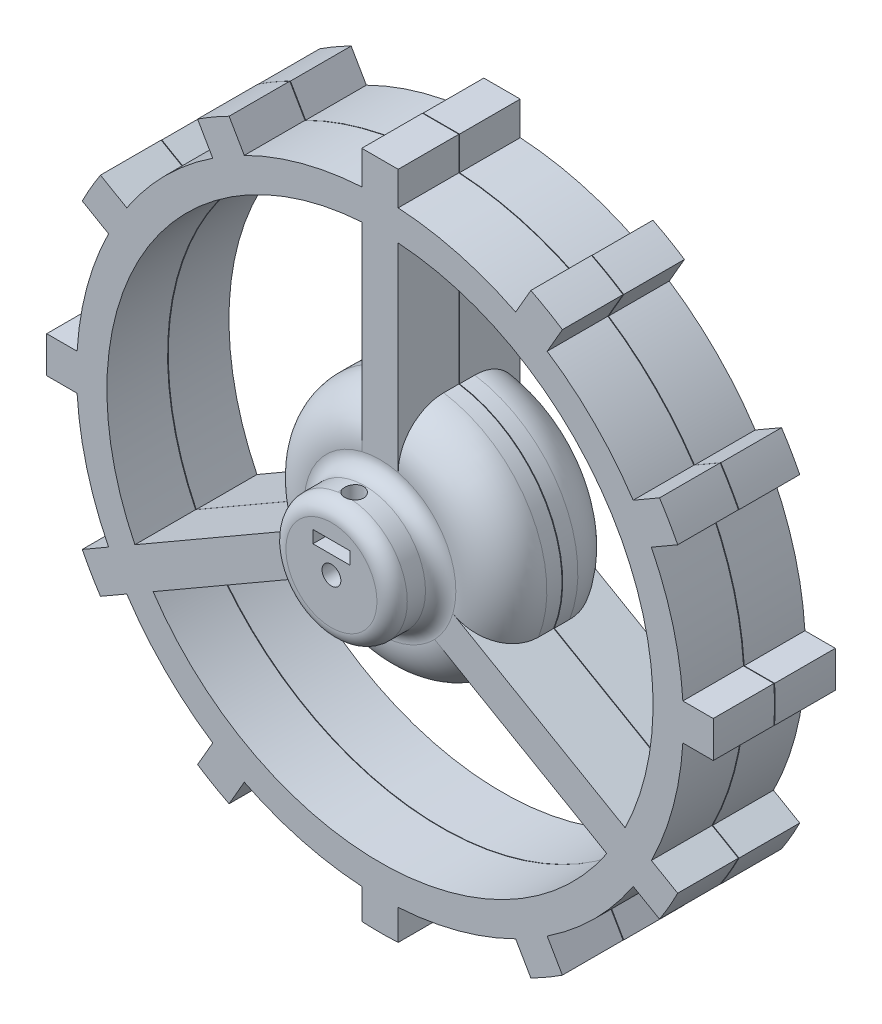
SolidWorks part; units mm, degrees
ref_plane "Front Plane" through (0, 0, 0) normal (0, 0, 1) x (1, 0, 0)
ref_plane "Top Plane" through (0, 0, 0) normal (0, 1, 0) x (1, 0, 0)
ref_plane "Right Plane" through (0, 0, 0) normal (1, 0, 0) x (0, 0, -1)
sketch "Sketch1" plane through (0, 0, 0) normal (0, 0, 1) x (1, 0, 0)
  line L0 (0, 50) -> (0, 55)
  line L1 (3, 49.9099) -> (3, 54.9181)
  line L2 (-3, 49.9099) -> (-3, 54.9181)
  line L3 (-3, 50) -> (-3, 55) construction
  line L4 (3, 50) -> (3, 55) construction
  line L5 (-3, 54.9181) -> (-3, 55.4203)
  line L6 (-3, 55.4203) -> (3, 55.4181)
  line L7 (3, 55.4181) -> (3, 54.9181)
  line L8 (0, 50) -> (0, 55) construction
  line L9 (0, 50) -> (0, 20)
  line L10 (22.3569, 44.7233) -> (24.861, 49.0605)
  line L11 (27.553, 41.7233) -> (30.0571, 46.0605)
  line L12 (25.1121, 49.4954) -> (30.3071, 46.4935)
  line L13 (30.3071, 46.4935) -> (30.0571, 46.0605)
  line L14 (24.861, 49.0605) -> (25.1121, 49.4954)
  line L15 (-3, 50) -> (-3, 20) construction
  line L17 (41.7233, 27.553) -> (46.0605, 30.0571)
  line L18 (44.7233, 22.3569) -> (49.0605, 24.861)
  line L19 (46.4954, 30.3082) -> (49.4935, 25.111)
  line L20 (49.4935, 25.111) -> (49.0605, 24.861)
  line L21 (46.0605, 30.0571) -> (46.4954, 30.3082)
  line L22 (3, 50) -> (3, 20) construction
  line L23 (-3, 50) -> (-3, 55)
  line L24 (49.9099, 3) -> (54.9181, 3)
  line L25 (49.9099, -3) -> (54.9181, -3)
  line L26 (55.4203, 3) -> (55.4181, -3)
  line L27 (55.4181, -3) -> (54.9181, -3)
  line L28 (54.9181, 3) -> (55.4203, 3)
  line L31 (44.7233, -22.3569) -> (49.0605, -24.861)
  line L32 (41.7233, -27.553) -> (46.0605, -30.0571)
  line L33 (49.4954, -25.1121) -> (46.4935, -30.3071)
  line L34 (46.4935, -30.3071) -> (46.0605, -30.0571)
  line L35 (49.0605, -24.861) -> (49.4954, -25.1121)
  line L37 (43.3013, -25) -> (17.3205, -10)
  line L38 (27.553, -41.7233) -> (30.0571, -46.0605)
  line L39 (22.3569, -44.7233) -> (24.861, -49.0605)
  line L40 (30.3082, -46.4954) -> (25.111, -49.4935)
  line L41 (25.111, -49.4935) -> (24.861, -49.0605)
  line L42 (30.0571, -46.0605) -> (30.3082, -46.4954)
  line L44 (-3, 50) -> (-3, 19.7737)
  line L45 (3, -49.9099) -> (3, -54.9181)
  line L46 (-3, -49.9099) -> (-3, -54.9181)
  line L47 (3, -55.4203) -> (-3, -55.4181)
  line L48 (-3, -55.4181) -> (-3, -54.9181)
  line L49 (3, -54.9181) -> (3, -55.4203)
  line L51 (3, 50) -> (3, 55)
  line L52 (-22.3569, -44.7233) -> (-24.861, -49.0605)
  line L53 (-27.553, -41.7233) -> (-30.0571, -46.0605)
  line L54 (-25.1121, -49.4954) -> (-30.3071, -46.4935)
  line L55 (-30.3071, -46.4935) -> (-30.0571, -46.0605)
  line L56 (-24.861, -49.0605) -> (-25.1121, -49.4954)
  line L58 (3, 50) -> (3, 19.7737)
  line L59 (-41.7233, -27.553) -> (-46.0605, -30.0571)
  line L60 (-44.7233, -22.3569) -> (-49.0605, -24.861)
  line L61 (-46.4954, -30.3082) -> (-49.4935, -25.111)
  line L62 (-49.4935, -25.111) -> (-49.0605, -24.861)
  line L63 (-46.0605, -30.0571) -> (-46.4954, -30.3082)
  line L65 (-43.3013, -25) -> (-17.3205, -10)
  line L66 (-49.9099, -3) -> (-54.9181, -3)
  line L67 (-49.9099, 3) -> (-54.9181, 3)
  line L68 (-55.4203, -3) -> (-55.4181, 3)
  line L69 (-55.4181, 3) -> (-54.9181, 3)
  line L70 (-54.9181, -3) -> (-55.4203, -3)
  line L73 (-44.7233, 22.3569) -> (-49.0605, 24.861)
  line L74 (-41.7233, 27.553) -> (-46.0605, 30.0571)
  line L75 (-49.4954, 25.1121) -> (-46.4935, 30.3071)
  line L76 (-46.4935, 30.3071) -> (-46.0605, 30.0571)
  line L77 (-49.0605, 24.861) -> (-49.4954, 25.1121)
  line L80 (-27.553, 41.7233) -> (-30.0571, 46.0605)
  line L81 (-22.3569, 44.7233) -> (-24.861, 49.0605)
  line L82 (-30.3082, 46.4954) -> (-25.111, 49.4935)
  line L83 (-25.111, 49.4935) -> (-24.861, 49.0605)
  line L84 (-30.0571, 46.0605) -> (-30.3082, 46.4954)
  line L87 (-41.8013, -27.5981) -> (-46.1314, -30.0981)
  line L88 (-41.8013, -27.5981) -> (-15.6245, -12.4849)
  line L89 (-44.8013, -22.4019) -> (-49.1314, -24.9019)
  line L90 (-44.8013, -22.4019) -> (-18.6245, -7.2888)
  line L91 (44.8013, -22.4019) -> (49.1314, -24.9019)
  line L92 (44.8013, -22.4019) -> (18.6245, -7.2888)
  line L93 (41.8013, -27.5981) -> (46.1314, -30.0981)
  line L94 (41.8013, -27.5981) -> (15.6245, -12.4849)
  line L96 (41.8013, -27.5981) -> (-1.5, -2.5981) construction
  line L98 (43.3013, -25) -> (0, 0) construction
  line L100 (44.8013, -22.4019) -> (1.5, 2.5981) construction
  line L103 (-44.8013, -22.4019) -> (-1.5, 2.5981) construction
  line L105 (-43.3013, -25) -> (0, 0) construction
  line L107 (-41.8013, -27.5981) -> (1.5, -2.5981) construction
  line L109 (3, -5.1962) -> (1.5, -2.5981) [skipped]
  line L110 (1.55, 0) -> (0, 0) [skipped]
  line L111 (1.3423, 0.775) -> (0, 0) [skipped]
  line L112 (0.775, 1.3423) -> (0, 0) [skipped]
  line L113 (-0.775, 1.3423) -> (0, 0) [skipped]
  line L114 (-1.3423, 0.775) -> (0, 0) [skipped]
  line L115 (-1.55, 0) -> (0, 0) [skipped]
  line L116 (-0.775, -1.3423) -> (0, 0) [skipped]
  line L117 (0, -1.55) -> (0, 0) [skipped]
  line L118 (-25, 43.3013) -> (-27.5, 47.6314) [skipped]
  line L119 (25, 43.3013) -> (27.5, 47.6314) [skipped]
  line L120 (43.3013, 25) -> (47.6314, 27.5) [skipped]
  line L121 (50, 0) -> (55, 0) [skipped]
  line L122 (43.3013, -25) -> (47.6314, -27.5) [skipped]
  line L123 (43.3013, -25) -> (47.6314, -27.5) construction
  line L124 (25, -43.3013) -> (27.5, -47.6314) [skipped]
  line L125 (0, -50) -> (0, -55) [skipped]
  line L126 (-25, -43.3013) -> (-27.5, -47.6314) [skipped]
  line L127 (-43.3013, -25) -> (-47.6314, -27.5) [skipped]
  line L128 (-43.3013, -25) -> (-47.6314, -27.5) construction
  line L129 (-50, 0) -> (-55, 0) [skipped]
  line L130 (-43.3013, 25) -> (-47.6314, 27.5) [skipped]
  arc A0 (-3, 54.9181) -> (3, 54.9181) centre (0, 0) ccw
  arc A1 (-27.553, 41.7233) -> (-41.7233, 27.553) centre (0, 0) ccw
  arc A2 (18.6245, -7.2888) -> (3, 19.7737) centre (0, 0) ccw
  circle A3 centre (0, 0) radius 1.55
  arc A4 (22.3569, 44.7233) -> (3, 49.9099) centre (0, 0) ccw
  arc A5 (41.7233, 27.553) -> (27.553, 41.7233) centre (0, 0) ccw
  arc A6 (49.9099, 3) -> (44.7233, 22.3569) centre (0, 0) ccw
  arc A7 (-49.9099, -3) -> (-44.7233, -22.3569) centre (0, 0) ccw
  arc A8 (-41.7233, -27.553) -> (-27.553, -41.7233) centre (0, 0) ccw
  arc A9 (-22.3569, -44.7233) -> (-3, -49.9099) centre (0, 0) ccw
  arc A10 (3, -49.9099) -> (22.3569, -44.7233) centre (0, 0) ccw
  arc A11 (27.553, -41.7233) -> (41.7233, -27.553) centre (0, 0) ccw
  arc A12 (44.7233, -22.3569) -> (49.9099, -3) centre (0, 0) ccw
  arc A13 (-44.7233, 22.3569) -> (-49.9099, 3) centre (0, 0) ccw
  arc A14 (-15.6245, -12.4849) -> (15.6245, -12.4849) centre (0, 0) ccw
  arc A15 (-3, 19.7737) -> (-18.6245, -7.2888) centre (0, 0) ccw
  arc A16 (-37.3844, -25.048) -> (37.3844, -25.048) centre (0, 0) ccw
  arc A17 (40.3844, -19.8519) -> (3, 44.8999) centre (0, 0) ccw
  arc A18 (-3, 44.8999) -> (-40.3844, -19.8519) centre (0, 0) ccw
  arc A19 (-3, 49.9099) -> (-22.3569, 44.7233) centre (0, 0) ccw
  point P109 (0, 0)
  dimension "D1" = 40
  dimension "D2" = 3.1
  dimension "D3" = 110
  dimension "D4" = 100
  dimension "D16" = 90
  dimension "D7" = 0.5021
  dimension "D8" = 0.5
  dimension "D9" = 12
  dimension "D5" = 3
  dimension "D6" = 3
  dimension "D10" = 3
  dimension "D11" = 3
  dimension "D12" = 3
  dimension "D13" = 3
  dimension "D14" = 3
  dimension "D15" = 3
extrude "Boss-Extrude2" add sketch "Sketch1" along normal blind 10 contours A16 L88 A8 L53 A0 L52 A9 L46 L45 A10 L39 L38 A11 L94 | L44 A15 L90 L60 A0 L59 L88 A14 L94 L32 L31 L92 A2 L58 L1 L7 L6 L5 L2 A3 | A17 L92 A12 L25 A0 L24 A6 L18 L17 A5 L11 L10 A4 L58 | L44 A19 L81 A0 L80 A1 L74 L73 A13 L67 L66 A7 L90 A18 region at (1.6987, 47.4049, 0) region at (12.7105, 47.4363, 0) region at (-24.38, 46.4467, 0) region at (28.3252, -46.108, 0)
sketch "Sketch2" plane through (0, 0, 10) normal (0, 0, 1) x (1, 0, 0)
  circle A0 centre (0, 0) radius 10
  circle A1 centre (0, 0) radius 1.55
  dimension "D1" = 20
  dimension "D2" = 3.1
extrude "Boss-Extrude3" add sketch "Sketch2" along normal blind 8
sketch "Sketch4" plane through (0.0198, 55.4192, 0) normal (0.0004, 1, 0) x (1, -0.0004, 0)
  line L0 (-0.0198, -10) -> (-0.0198, -14.25)
  line L7 (-3.0198, -10) -> (2.9802, -10) construction
  circle A0 centre (-0.0198, -14.25) radius 1.55
  dimension "D2" = 3.1
  dimension "D1" = 4.25
sketch "Sketch7" plane through (0, 0, 0) normal (0, 0, -1) x (-1, 0, 0)
  line L0 (-0.1121, 50.0766) -> (-0.1121, 55.0766)
  line L1 (2.8879, 49.9866) -> (2.8879, 54.9948)
  line L2 (-3.1121, 49.9866) -> (-3.1121, 54.9948)
  line L3 (-3.1121, 54.9948) -> (-3.1121, 55.4969)
  line L4 (-3.1121, 55.4969) -> (2.8879, 55.4948)
  line L5 (2.8879, 55.4948) -> (2.8879, 54.9948)
  line L6 (-0.1121, 50.0766) -> (-0.1121, 20.0766)
  line L7 (22.2448, 44.7999) -> (24.7489, 49.1371)
  line L8 (27.4409, 41.7999) -> (29.945, 46.1371)
  line L9 (24.9999, 49.572) -> (30.195, 46.5701)
  line L10 (30.195, 46.5701) -> (29.945, 46.1371)
  line L11 (24.7489, 49.1371) -> (24.9999, 49.572)
  line L12 (41.6111, 27.6297) -> (45.9484, 30.1338)
  line L13 (44.6111, 22.4335) -> (48.9484, 24.9376)
  line L14 (46.3832, 30.3849) -> (49.3814, 25.1876)
  line L15 (49.3814, 25.1876) -> (48.9484, 24.9376)
  line L16 (45.9484, 30.1338) -> (46.3832, 30.3849)
  line L17 (-3.1121, 50.0766) -> (-3.1121, 55.0766)
  line L18 (49.7978, 3.0766) -> (54.806, 3.0766)
  line L19 (49.7978, -2.9234) -> (54.806, -2.9234)
  line L20 (55.3081, 3.0766) -> (55.306, -2.9234)
  line L21 (55.306, -2.9234) -> (54.806, -2.9234)
  line L22 (54.806, 3.0766) -> (55.3081, 3.0766)
  line L23 (44.6111, -22.2802) -> (48.9484, -24.7843)
  line L24 (41.6111, -27.4764) -> (45.9484, -29.9805)
  line L25 (49.3832, -25.0354) -> (46.3814, -30.2305)
  line L26 (46.3814, -30.2305) -> (45.9484, -29.9805)
  line L27 (48.9484, -24.7843) -> (49.3832, -25.0354)
  line L28 (43.1891, -24.9234) -> (17.2084, -9.9234)
  line L29 (27.4409, -41.6466) -> (29.945, -45.9838)
  line L30 (22.2448, -44.6466) -> (24.7489, -48.9838)
  line L31 (30.1961, -46.4187) -> (24.9989, -49.4169)
  line L32 (24.9989, -49.4169) -> (24.7489, -48.9838)
  line L33 (29.945, -45.9838) -> (30.1961, -46.4187)
  line L34 (-3.1121, 50.0766) -> (-3.1121, 19.8504)
  line L35 (2.8879, -49.8333) -> (2.8879, -54.8415)
  line L36 (-3.1121, -49.8333) -> (-3.1121, -54.8415)
  line L37 (2.8879, -55.3436) -> (-3.1121, -55.3415)
  line L38 (-3.1121, -55.3415) -> (-3.1121, -54.8415)
  line L39 (2.8879, -54.8415) -> (2.8879, -55.3436)
  line L40 (2.8879, 50.0766) -> (2.8879, 55.0766)
  line L41 (-22.469, -44.6466) -> (-24.9731, -48.9838)
  line L42 (-27.6652, -41.6466) -> (-30.1693, -45.9838)
  line L43 (-25.2242, -49.4187) -> (-30.4193, -46.4169)
  line L44 (-30.4193, -46.4169) -> (-30.1693, -45.9838)
  line L45 (-24.9731, -48.9838) -> (-25.2242, -49.4187)
  line L46 (2.8879, 50.0766) -> (2.8879, 19.8504)
  line L47 (-41.8354, -27.4764) -> (-46.1726, -29.9805)
  line L48 (-44.8354, -22.2802) -> (-49.1726, -24.7843)
  line L49 (-46.6075, -30.2316) -> (-49.6056, -25.0343)
  line L50 (-49.6056, -25.0343) -> (-49.1726, -24.7843)
  line L51 (-46.1726, -29.9805) -> (-46.6075, -30.2316)
  line L52 (-43.4134, -24.9234) -> (-17.4326, -9.9234)
  line L53 (-50.022, -2.9234) -> (-55.0302, -2.9234)
  line L54 (-50.022, 3.0766) -> (-55.0302, 3.0766)
  line L55 (-55.5324, -2.9234) -> (-55.5302, 3.0766)
  line L56 (-55.5302, 3.0766) -> (-55.0302, 3.0766)
  line L57 (-55.0302, -2.9234) -> (-55.5324, -2.9234)
  line L58 (-44.8354, 22.4335) -> (-49.1726, 24.9376)
  line L59 (-41.8354, 27.6297) -> (-46.1726, 30.1338)
  line L60 (-49.6075, 25.1887) -> (-46.6056, 30.3838)
  line L61 (-46.6056, 30.3838) -> (-46.1726, 30.1338)
  line L62 (-49.1726, 24.9376) -> (-49.6075, 25.1887)
  line L63 (-27.6652, 41.7999) -> (-30.1693, 46.1371)
  line L64 (-22.469, 44.7999) -> (-24.9731, 49.1371)
  line L65 (-30.4203, 46.572) -> (-25.2231, 49.5701)
  line L66 (-25.2231, 49.5701) -> (-24.9731, 49.1371)
  line L67 (-30.1693, 46.1371) -> (-30.4203, 46.572)
  line L68 (-41.9134, -27.5214) -> (-46.2435, -30.0214)
  line L69 (-41.9134, -27.5214) -> (-15.7367, -12.4083)
  line L70 (-44.9134, -22.3253) -> (-49.2435, -24.8253)
  line L71 (-44.9134, -22.3253) -> (-18.7367, -7.2121)
  line L72 (44.6891, -22.3253) -> (49.0193, -24.8253)
  line L73 (44.6891, -22.3253) -> (18.5124, -7.2121)
  line L74 (41.6891, -27.5214) -> (46.0193, -30.0214)
  line L75 (41.6891, -27.5214) -> (15.5124, -12.4083)
  line L76 (2.8879, -5.1195) -> (1.3879, -2.5214)
  line L77 (1.4379, 0.0766) -> (-0.1121, 0.0766)
  line L78 (1.2302, 0.8516) -> (-0.1121, 0.0766)
  line L79 (0.6629, 1.419) -> (-0.1121, 0.0766)
  line L80 (-0.8871, 1.419) -> (-0.1121, 0.0766)
  line L81 (-1.4545, 0.8516) -> (-0.1121, 0.0766)
  line L82 (-1.6621, 0.0766) -> (-0.1121, 0.0766)
  line L83 (-0.8871, -1.2657) -> (-0.1121, 0.0766)
  line L84 (-0.1121, -1.4734) -> (-0.1121, 0.0766)
  line L85 (-25.1121, 43.3779) -> (-27.6121, 47.708)
  line L86 (24.8879, 43.3779) -> (27.3879, 47.708)
  line L87 (43.1891, 25.0766) -> (47.5193, 27.5766)
  line L88 (49.8879, 0.0766) -> (54.8879, 0.0766)
  line L89 (43.1891, -24.9234) -> (47.5193, -27.4234)
  line L90 (24.8879, -43.2246) -> (27.3879, -47.5547)
  line L91 (-0.1121, -49.9234) -> (-0.1121, -54.9234)
  line L92 (-25.1121, -43.2246) -> (-27.6121, -47.5547)
  line L93 (-43.4134, -24.9234) -> (-47.7435, -27.4234)
  line L94 (-50.1121, 0.0766) -> (-55.1121, 0.0766)
  line L95 (-43.4134, 25.0766) -> (-47.7435, 27.5766)
  arc A0 (-3.1121, 54.9948) -> (2.8879, 54.9948) centre (-0.1121, 0.0766) ccw
  arc A1 (-27.6652, 41.7999) -> (-41.8354, 27.6297) centre (-0.1121, 0.0766) ccw
  arc A2 (18.5124, -7.2121) -> (2.8879, 19.8504) centre (-0.1121, 0.0766) ccw
  circle A3 centre (-0.1121, 0.0766) radius 1.55
  arc A4 (22.2448, 44.7999) -> (2.8879, 49.9866) centre (-0.1121, 0.0766) ccw
  arc A5 (41.6111, 27.6297) -> (27.4409, 41.7999) centre (-0.1121, 0.0766) ccw
  arc A6 (49.7978, 3.0766) -> (44.6111, 22.4335) centre (-0.1121, 0.0766) ccw
  arc A7 (-50.022, -2.9234) -> (-44.8354, -22.2802) centre (-0.1121, 0.0766) ccw
  arc A8 (-41.8354, -27.4764) -> (-27.6652, -41.6466) centre (-0.1121, 0.0766) ccw
  arc A9 (-22.469, -44.6466) -> (-3.1121, -49.8333) centre (-0.1121, 0.0766) ccw
  arc A10 (2.8879, -49.8333) -> (22.2448, -44.6466) centre (-0.1121, 0.0766) ccw
  arc A11 (27.4409, -41.6466) -> (41.6111, -27.4764) centre (-0.1121, 0.0766) ccw
  arc A12 (44.6111, -22.2802) -> (49.7978, -2.9234) centre (-0.1121, 0.0766) ccw
  arc A13 (-44.8354, 22.4335) -> (-50.022, 3.0766) centre (-0.1121, 0.0766) ccw
  arc A14 (-15.7367, -12.4083) -> (15.5124, -12.4083) centre (-0.1121, 0.0766) ccw
  arc A15 (-3.1121, 19.8504) -> (-18.7367, -7.2121) centre (-0.1121, 0.0766) ccw
  arc A16 (-37.4966, -24.9714) -> (37.2723, -24.9714) centre (-0.1121, 0.0766) ccw
  arc A17 (40.2723, -19.7752) -> (2.8879, 44.9765) centre (-0.1121, 0.0766) ccw
  arc A18 (-3.1121, 44.9765) -> (-40.4966, -19.7752) centre (-0.1121, 0.0766) ccw
  arc A19 (-3.1121, 49.9866) -> (-22.469, 44.7999) centre (-0.1121, 0.0766) ccw
  point P86 (-0.1121, 0.0766)
extrude "Boss-Extrude5" add sketch "Sketch7" along normal blind 10 contours L34 A15 L71 L48 A0 L47 L69 A14 L75 L24 L23 L73 A2 L46 L1 L5 L4 L3 L2 | L34 A19 L64 A0 L63 A1 L59 L58 A13 L54 L53 A7 L71 A18 | A16 L69 A8 L42 A0 L41 A9 L36 L35 A10 L30 L29 A11 L75 | A17 L73 A12 L19 A0 L18 A6 L13 L12 A5 L8 L7 A4 L46 region at (-1.5866, 47.4816, 0) region at (-12.5984, 47.513, 0) region at (24.4921, 46.5234, 0) region at (-28.2131, -46.0313, 0)
fillet "Fillet3" radius 7.5 6 edges at (17.3205, 10, 10) (-17.3205, 10, 10) (0, -20, 10) (-17.2084, 10.0766, -10) (0.1121, -19.9234, -10) (17.4326, 10.0766, -10)
fillet "Fillet4" radius 2.5 1 edges at (10, 0, 18)
extrude "Cut-Extrude3" cut sketch "Sketch4" against normal blind 56 contours A0 region at (-1.065, 55.4196, 15.315)
sketch "Sketch8" plane through (0, 0, 18) normal (0, 0, 1) x (1, 0, 0)
  line L0 (0, 7.5) -> (0, 5)
  line L1 (0, 5) -> (3.05, 5)
  line L2 (3.05, 5) -> (3.05, 2.95)
  line L3 (3.05, 2.95) -> (-3.05, 2.95)
  line L4 (-3.05, 2.95) -> (-3.05, 5)
  line L5 (-3.05, 5) -> (0, 5)
  circle A0 centre (0, 0) radius 7.5 construction
  dimension "D1" = 6.1
  dimension "D2" = 3.05
  dimension "D3" = 2.05
  dimension "D4" = 2.5
extrude "Cut-Extrude4" cut sketch "Sketch8" against normal blind 5.1 contours L5 L4 L3 L2 L1 region at (0, 3.975, 18)
fillet "Fillet5" radius 2.5 1 edges at (10, 0, 10)
